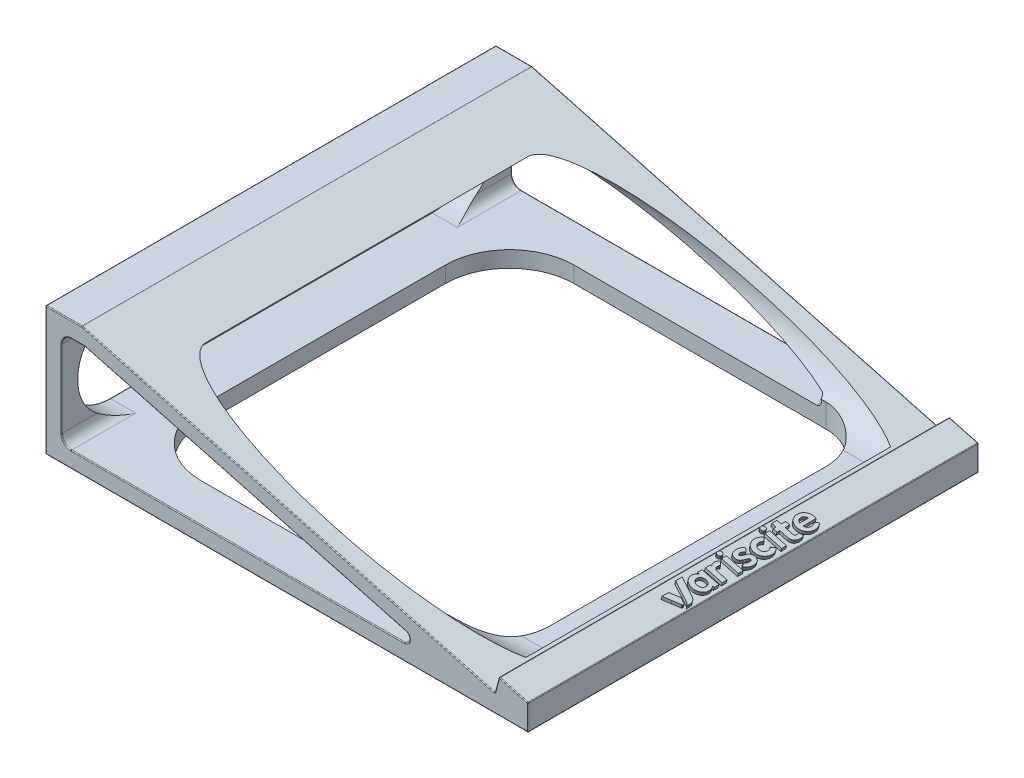
SolidWorks part; units mm, degrees
material "ABS"
ref_plane "Ebene vorne" through (0, 0, 0) normal (1, 0, 0) x (0, 1, 0)
ref_plane "Ebene oben" through (0, 0, 0) normal (0, 0, 1) x (0, 1, 0)
ref_plane "Ebene rechts" through (0, 0, 0) normal (0, 1, 0) x (-1, 0, 0)
sketch "Basis" plane through (0, 0, 0) normal (0, 0, 1) x (0, 1, 0)
  line L0 (0, 0) -> (0, 150)
  line L1 (0, 0) -> (8, 0)
  line L2 (8, 0) -> (10.4201, 9.032)
  line L3 (0, 150) -> (40, 150)
  line L4 (40, 150) -> (40, 138.7441)
  line L5 (40, 138.7441) -> (5.5905, 10.3261)
  line L6 (5.5905, 10.3261) -> (10.4201, 9.032)
  dimension "D1" = 15
  dimension "D2" = 90
  dimension "D3" = 8
  dimension "D4" = 150
  dimension "D5" = 15
  dimension "D6" = 40
  dimension "D8" = 5
extrude "Aufsatz-Linear austragen1" add sketch "Basis" along normal blind 140
sketch "Schnitt Boden" plane through (0.3591, 0, 0) normal (0, 1, 0) x (-1, 0, 0)
  line L0 (139.1032, 140) -> (139.1032, 0) construction
  line L4 (35.6851, 128) -> (114.1032, 128)
  line L6 (20.6851, 113) -> (20.6851, 27)
  line L7 (35.6851, 12) -> (114.1032, 12)
  line L8 (134.1032, 108) -> (134.1032, 32)
  line L9 (10.6851, 140) -> (139.1032, 140) construction
  line L10 (10.6851, 0) -> (139.1032, 0) construction
  line L11 (10.6851, 140) -> (10.6851, 0) construction
  arc A2 (35.6851, 128) -> (20.6851, 113) centre (35.6851, 113) ccw
  arc A3 (20.6851, 27) -> (35.6851, 12) centre (35.6851, 27) ccw
  arc A4 (134.1032, 32) -> (114.1032, 12) centre (114.1032, 32) cw
  arc A5 (134.1032, 108) -> (114.1032, 128) centre (114.1032, 108) ccw
  point P20 (10.6851, 70)
  dimension "D1" = 15
  dimension "D3" = 12
  dimension "D6" = 20
  dimension "D2" = 5
  dimension "D4" = 12
  dimension "D5" = 10
sketch "Schnitt Hinten" plane through (-150, 0, 0) normal (-1, 0, 0) x (0, -1, 0)
  line L0 (-20, 120) -> (-20, 20) construction
  line L1 (-5, 120) -> (-5, 20)
  line L2 (-35, 120) -> (-35, 20)
  line L3 (-40, 0) -> (0, 0) construction
  line L4 (0, 140) -> (0, 0) construction
  arc A0 (-5, 120) -> (-35, 120) centre (-20, 120) ccw
  arc A1 (-35, 20) -> (-5, 20) centre (-20, 20) ccw
  point P2 (-20, 70)
  dimension "D1" = 70
  dimension "D2" = 20
extrude "Schnitt Hinten austragen" cut sketch "Schnitt Hinten" against normal blind 136
extrude "Schnitt Boden austragen" cut sketch "Schnitt Boden" along normal blind 10
sketch "Schnitt Seite" plane through (0, 0, 140) normal (0, 0, 1) x (1, 0, 0)
  line L0 (-142, 35) -> (-137.7635, 35)
  line L1 (-137.7635, 35) -> (-37.9725, 8.2611)
  line L2 (-36.8607, 6.8122) -> (-36.8607, 6.5)
  line L3 (-38.3607, 5) -> (-142, 5)
  line L4 (-145, 8) -> (-145, 32)
  line L5 (-150, 40) -> (-150, 0) construction
  line L6 (-150, 0) -> (0, 0) construction
  line L7 (-10.3261, 5.5905) -> (-138.7441, 40) construction
  arc A0 (-145, 32) -> (-142, 35) centre (-142, 32) cw
  arc A1 (-142, 5) -> (-145, 8) centre (-142, 8) cw
  arc A2 (-38.3607, 5) -> (-36.8607, 6.5) centre (-38.3607, 6.5) ccw
  arc A3 (-36.8607, 6.8122) -> (-37.9725, 8.2611) centre (-38.3607, 6.8122) ccw
  dimension "D5" = 3
  dimension "D6" = 3
  dimension "D7" = 1.5
  dimension "D1" = 5
  dimension "D2" = 5
  dimension "D3" = 0
  dimension "D4" = 5
extrude "Schnitt Seite austragen" cut sketch "Schnitt Seite" against normal blind 140
fillet "Katenverrundung austragen" radius 0.25 43 edges at (-36.8607, 6.6561, 140) (0, 0, 70) (0, 4, 0) (-36.8607, 6.6561, 0) (-37.1707, 7.7253, 0) (-37.3001, 5.4393, 0) (-139.8817, 35, 0) (-87.868, 21.6305, 0) (-144.1213, 34.1213, 0) (-144.1213, 5.8787, 0) (-145, 20, 0) (-150, 35, 70) (-150, 20, 135) (-150, 20, 5) (-150, 5, 70) (-150, 0, 70) (-90.1804, 5, 0) (-75, 0, 0) (0, 8, 70) (-4.516, 9.2101, 0) (-9.679, 8.0053, 0) (-10.3261, 5.5905, 70) (-9.032, 10.4201, 70) (-138.7441, 40, 70) (-37.3001, 5.4393, 140) (-144.1213, 5.8787, 140) (-144.1213, 34.1213, 140) (-139.8817, 35, 140) (-87.868, 21.6305, 140) (-145, 20, 140) (-37.1707, 7.7253, 140) (-90.1804, 5, 140) (-75, 0, 140) (0, 4, 140) (-4.516, 9.2101, 140) (-9.679, 8.0053, 140) (-150, 20, 140) (-144.3721, 40, 140) (-74.5351, 22.7952, 140) (-74.5351, 22.7952, 0) (-144.3721, 40, 0) (-150, 20, 0) (-150, 40, 70)
sketch "Skizze Logo" plane through (2, 7.4641, 0) normal (0.2588, 0.9659, 0) x (-0.9659, 0.2588, 0)
  line L0 (8.7653, 83.336) -> (8.7223, 83.5503)
  line L1 (8.7223, 83.5503) -> (8.6617, 83.7574)
  line L2 (8.6617, 83.7574) -> (8.5841, 83.9565)
  line L3 (8.5841, 83.9565) -> (8.4904, 84.1471)
  line L4 (8.4904, 84.1471) -> (8.3812, 84.3284)
  line L5 (8.3812, 84.3284) -> (8.2572, 84.4998)
  line L6 (8.2572, 84.4998) -> (8.1193, 84.6607)
  line L7 (8.1193, 84.6607) -> (7.968, 84.8103)
  line L8 (7.968, 84.8103) -> (7.8042, 84.948)
  line L9 (7.8042, 84.948) -> (7.6286, 85.0731)
  line L10 (7.6286, 85.0731) -> (7.4418, 85.1851)
  line L11 (7.4418, 85.1851) -> (7.2447, 85.2831)
  line L12 (7.2447, 85.2831) -> (7.0379, 85.3666)
  line L13 (7.0379, 85.3666) -> (6.8221, 85.4349)
  line L14 (6.8221, 85.4349) -> (6.5982, 85.4873)
  line L15 (6.5982, 85.4873) -> (6.3668, 85.5232)
  line L16 (6.3668, 85.5232) -> (6.1055, 85.5395)
  line L17 (6.1055, 85.5395) -> (5.8095, 85.5358)
  line L18 (5.8095, 85.5358) -> (5.5207, 85.5139)
  line L19 (5.5207, 85.5139) -> (5.2806, 85.4757)
  line L20 (5.2806, 85.4757) -> (5.0781, 85.4227)
  line L21 (5.0781, 85.4227) -> (4.8833, 85.3574)
  line L22 (4.8833, 85.3574) -> (4.6967, 85.2803)
  line L23 (4.6967, 85.2803) -> (4.5186, 85.1917)
  line L24 (4.5186, 85.1917) -> (4.3495, 85.0921)
  line L25 (4.3495, 85.0921) -> (4.1898, 84.9818)
  line L26 (4.1898, 84.9818) -> (4.0398, 84.8613)
  line L27 (4.0398, 84.8613) -> (3.9, 84.731)
  line L28 (3.9, 84.731) -> (3.7708, 84.5913)
  line L29 (3.7708, 84.5913) -> (3.6526, 84.4425)
  line L30 (3.6526, 84.4425) -> (3.5458, 84.2852)
  line L31 (3.5458, 84.2852) -> (3.4507, 84.1196)
  line L32 (3.4507, 84.1196) -> (3.3679, 83.9462)
  line L33 (3.3679, 83.9462) -> (3.2976, 83.7654)
  line L34 (3.2976, 83.7654) -> (3.2404, 83.5777)
  line L35 (3.2404, 83.5777) -> (3.1965, 83.3833)
  line L36 (3.1965, 83.3833) -> (3.1685, 83.1466)
  line L37 (3.1685, 83.1466) -> (3.1596, 82.8688)
  line L38 (3.1596, 82.8688) -> (3.1699, 82.5946)
  line L39 (3.1699, 82.5946) -> (3.1992, 82.3684)
  line L40 (3.1992, 82.3684) -> (3.274, 82.0965)
  line L41 (3.274, 82.0965) -> (3.3828, 81.8376)
  line L42 (3.3828, 81.8376) -> (3.5252, 81.5928)
  line L43 (3.5252, 81.5928) -> (3.7004, 81.3632)
  line L44 (3.7004, 81.3632) -> (3.7878, 81.262)
  line L45 (3.7878, 81.262) -> (3.523, 81.262)
  line L46 (3.523, 81.262) -> (3.2582, 81.262)
  line L47 (3.2582, 81.262) -> (3.2582, 80.5244)
  line L48 (3.2582, 80.5244) -> (3.2582, 79.7869)
  line L49 (3.2582, 79.7869) -> (5.9706, 79.7869)
  line L50 (5.9706, 79.7869) -> (8.6831, 79.7869)
  line L51 (8.6831, 79.7869) -> (8.6831, 80.5244)
  line L52 (8.6831, 80.5244) -> (8.6831, 81.262)
  line L53 (8.6831, 81.262) -> (8.4181, 81.262)
  line L54 (8.4181, 81.262) -> (8.1531, 81.262)
  line L55 (8.1531, 81.262) -> (8.2585, 81.3751)
  line L56 (8.2585, 81.3751) -> (8.4117, 81.5635)
  line L57 (8.4117, 81.5635) -> (8.5405, 81.7728)
  line L58 (8.5405, 81.7728) -> (8.6441, 82.0005)
  line L59 (8.6441, 82.0005) -> (8.7221, 82.2444)
  line L60 (8.7221, 82.2444) -> (8.7738, 82.5022)
  line L61 (8.7738, 82.5022) -> (8.7986, 82.7716)
  line L62 (8.7986, 82.7716) -> (8.796, 83.0503)
  line L63 (8.796, 83.0503) -> (8.7653, 83.336)
  line L64 (7.4097, 82.2247) -> (7.3649, 82.0826)
  line L65 (7.3649, 82.0826) -> (7.3051, 81.9471)
  line L66 (7.3051, 81.9471) -> (7.2312, 81.8194)
  line L67 (7.2312, 81.8194) -> (7.1442, 81.7007)
  line L68 (7.1442, 81.7007) -> (7.0451, 81.5922)
  line L69 (7.0451, 81.5922) -> (6.9348, 81.495)
  line L70 (6.9348, 81.495) -> (6.8142, 81.4103)
  line L71 (6.8142, 81.4103) -> (6.6844, 81.3393)
  line L72 (6.6844, 81.3393) -> (6.5039, 81.2616)
  line L73 (6.5039, 81.2616) -> (6.342, 81.2133)
  line L74 (6.342, 81.2133) -> (6.1728, 81.1888)
  line L75 (6.1728, 81.1888) -> (5.9706, 81.1825)
  line L76 (5.9706, 81.1825) -> (5.8016, 81.1888)
  line L77 (5.8016, 81.1888) -> (5.6459, 81.2066)
  line L78 (5.6459, 81.2066) -> (5.5019, 81.2367)
  line L79 (5.5019, 81.2367) -> (5.3678, 81.2798)
  line L80 (5.3678, 81.2798) -> (5.2421, 81.3364)
  line L81 (5.2421, 81.3364) -> (5.123, 81.4072)
  line L82 (5.123, 81.4072) -> (5.0087, 81.493)
  line L83 (5.0087, 81.493) -> (4.8977, 81.5942)
  line L84 (4.8977, 81.5942) -> (4.8015, 81.6985)
  line L85 (4.8015, 81.6985) -> (4.7191, 81.8071)
  line L86 (4.7191, 81.8071) -> (4.65, 81.9208)
  line L87 (4.65, 81.9208) -> (4.594, 82.0402)
  line L88 (4.594, 82.0402) -> (4.5509, 82.1661)
  line L89 (4.5509, 82.1661) -> (4.5204, 82.2992)
  line L90 (4.5204, 82.2992) -> (4.5021, 82.4401)
  line L91 (4.5021, 82.4401) -> (4.4959, 82.5895)
  line L92 (4.4959, 82.5895) -> (4.5046, 82.7693)
  line L93 (4.5046, 82.7693) -> (4.5314, 82.9407)
  line L94 (4.5314, 82.9407) -> (4.5759, 83.103)
  line L95 (4.5759, 83.103) -> (4.6376, 83.2551)
  line L96 (4.6376, 83.2551) -> (4.716, 83.3962)
  line L97 (4.716, 83.3962) -> (4.8109, 83.5254)
  line L98 (4.8109, 83.5254) -> (4.9216, 83.6418)
  line L99 (4.9216, 83.6418) -> (5.0478, 83.7444)
  line L100 (5.0478, 83.7444) -> (5.1467, 83.8087)
  line L101 (5.1467, 83.8087) -> (5.2515, 83.8648)
  line L102 (5.2515, 83.8648) -> (5.4773, 83.9516)
  line L103 (5.4773, 83.9516) -> (5.7229, 84.0043)
  line L104 (5.7229, 84.0043) -> (5.9856, 84.022)
  line L105 (5.9856, 84.022) -> (6.2383, 84.0043)
  line L106 (6.2383, 84.0043) -> (6.474, 83.9522)
  line L107 (6.474, 83.9522) -> (6.6904, 83.8674)
  line L108 (6.6904, 83.8674) -> (6.885, 83.7516)
  line L109 (6.885, 83.7516) -> (7.0557, 83.6063)
  line L110 (7.0557, 83.6063) -> (7.2001, 83.4334)
  line L111 (7.2001, 83.4334) -> (7.3159, 83.2343)
  line L112 (7.3159, 83.2343) -> (7.4008, 83.0108)
  line L113 (7.4008, 83.0108) -> (7.4319, 82.8374)
  line L114 (7.4319, 82.8374) -> (7.4441, 82.6215)
  line L115 (7.4441, 82.6215) -> (7.4368, 82.4037)
  line L116 (7.4368, 82.4037) -> (7.4097, 82.2247)
  line L117 (8.7651, 50.6421) -> (8.7206, 50.846)
  line L118 (8.7206, 50.846) -> (8.6623, 51.0448)
  line L119 (8.6623, 51.0448) -> (8.5907, 51.238)
  line L120 (8.5907, 51.238) -> (8.5066, 51.4248)
  line L121 (8.5066, 51.4248) -> (8.4104, 51.6046)
  line L122 (8.4104, 51.6046) -> (8.3029, 51.7765)
  line L123 (8.3029, 51.7765) -> (8.1846, 51.94)
  line L124 (8.1846, 51.94) -> (8.0562, 52.0943)
  line L125 (8.0562, 52.0943) -> (7.9183, 52.2387)
  line L126 (7.9183, 52.2387) -> (7.7716, 52.3726)
  line L127 (7.7716, 52.3726) -> (7.6166, 52.4951)
  line L128 (7.6166, 52.4951) -> (7.4541, 52.6057)
  line L129 (7.4541, 52.6057) -> (7.2845, 52.7036)
  line L130 (7.2845, 52.7036) -> (7.1086, 52.7881)
  line L131 (7.1086, 52.7881) -> (6.9269, 52.8585)
  line L132 (6.9269, 52.8585) -> (6.7401, 52.9141)
  line L133 (6.7401, 52.9141) -> (6.4354, 52.975)
  line L134 (6.4354, 52.975) -> (6.1284, 53.0047)
  line L135 (6.1284, 53.0047) -> (5.8223, 53.0036)
  line L136 (5.8223, 53.0036) -> (5.5208, 52.9725)
  line L137 (5.5208, 52.9725) -> (5.2272, 52.9116)
  line L138 (5.2272, 52.9116) -> (4.9449, 52.8217)
  line L139 (4.9449, 52.8217) -> (4.6774, 52.7032)
  line L140 (4.6774, 52.7032) -> (4.428, 52.5566)
  line L141 (4.428, 52.5566) -> (4.1935, 52.3806)
  line L142 (4.1935, 52.3806) -> (3.9807, 52.1824)
  line L143 (3.9807, 52.1824) -> (3.7902, 51.9629)
  line L144 (3.7902, 51.9629) -> (3.6227, 51.7231)
  line L145 (3.6227, 51.7231) -> (3.4787, 51.464)
  line L146 (3.4787, 51.464) -> (3.359, 51.1866)
  line L147 (3.359, 51.1866) -> (3.264, 50.8919)
  line L148 (3.264, 50.8919) -> (3.1944, 50.5808)
  line L149 (3.1944, 50.5808) -> (3.1649, 50.3128)
  line L150 (3.1649, 50.3128) -> (3.1558, 49.9902)
  line L151 (3.1558, 49.9902) -> (3.1668, 49.6655)
  line L152 (3.1668, 49.6655) -> (3.1978, 49.3911)
  line L153 (3.1978, 49.3911) -> (3.244, 49.1706)
  line L154 (3.244, 49.1706) -> (3.3031, 48.959)
  line L155 (3.3031, 48.959) -> (3.3748, 48.7571)
  line L156 (3.3748, 48.7571) -> (3.4588, 48.5654)
  line L157 (3.4588, 48.5654) -> (3.5549, 48.3844)
  line L158 (3.5549, 48.3844) -> (3.6626, 48.2148)
  line L159 (3.6626, 48.2148) -> (3.7818, 48.0572)
  line L160 (3.7818, 48.0572) -> (3.9121, 47.9122)
  line L161 (3.9121, 47.9122) -> (4.0791, 47.7418)
  line L162 (4.0791, 47.7418) -> (4.504, 48.1792)
  line L163 (4.504, 48.1792) -> (4.9289, 48.6165)
  line L164 (4.9289, 48.6165) -> (4.7974, 48.7619)
  line L165 (4.7974, 48.7619) -> (4.7038, 48.8749)
  line L166 (4.7038, 48.8749) -> (4.6229, 48.9934)
  line L167 (4.6229, 48.9934) -> (4.5544, 49.1186)
  line L168 (4.5544, 49.1186) -> (4.4979, 49.2514)
  line L169 (4.4979, 49.2514) -> (4.4529, 49.3929)
  line L170 (4.4529, 49.3929) -> (4.419, 49.5442)
  line L171 (4.419, 49.5442) -> (4.3959, 49.7065)
  line L172 (4.3959, 49.7065) -> (4.3832, 49.8806)
  line L173 (4.3832, 49.8806) -> (4.3808, 50.054)
  line L174 (4.3808, 50.054) -> (4.389, 50.2147)
  line L175 (4.389, 50.2147) -> (4.4085, 50.3645)
  line L176 (4.4085, 50.3645) -> (4.4395, 50.505)
  line L177 (4.4395, 50.505) -> (4.4825, 50.6377)
  line L178 (4.4825, 50.6377) -> (4.5381, 50.7643)
  line L179 (4.5381, 50.7643) -> (4.6065, 50.8864)
  line L180 (4.6065, 50.8864) -> (4.6883, 51.0056)
  line L181 (4.6883, 51.0056) -> (4.8341, 51.1662)
  line L182 (4.8341, 51.1662) -> (5.0108, 51.3051)
  line L183 (5.0108, 51.3051) -> (5.2067, 51.4145)
  line L184 (5.2067, 51.4145) -> (5.4104, 51.4868)
  line L185 (5.4104, 51.4868) -> (5.4707, 51.5019)
  line L186 (5.4707, 51.5019) -> (5.4768, 49.4602)
  line L187 (5.4768, 49.4602) -> (5.4829, 47.4184)
  line L188 (5.4829, 47.4184) -> (5.5781, 47.3951)
  line L189 (5.5781, 47.3951) -> (5.7816, 47.3785)
  line L190 (5.7816, 47.3785) -> (6.1372, 47.3713)
  line L191 (6.1372, 47.3713) -> (6.5653, 47.3805)
  line L192 (6.5653, 47.3805) -> (6.6938, 47.3993)
  line L193 (6.6938, 47.3993) -> (6.8321, 47.4336)
  line L194 (6.8321, 47.4336) -> (7.0177, 47.4911)
  line L195 (7.0177, 47.4911) -> (7.1969, 47.561)
  line L196 (7.1969, 47.561) -> (7.3691, 47.6425)
  line L197 (7.3691, 47.6425) -> (7.534, 47.7353)
  line L198 (7.534, 47.7353) -> (7.691, 47.8389)
  line L199 (7.691, 47.8389) -> (7.8398, 47.9526)
  line L200 (7.8398, 47.9526) -> (7.9797, 48.0761)
  line L201 (7.9797, 48.0761) -> (8.1104, 48.2088)
  line L202 (8.1104, 48.2088) -> (8.2314, 48.3501)
  line L203 (8.2314, 48.3501) -> (8.3422, 48.4997)
  line L204 (8.3422, 48.4997) -> (8.4423, 48.6569)
  line L205 (8.4423, 48.6569) -> (8.5313, 48.8212)
  line L206 (8.5313, 48.8212) -> (8.6087, 48.9922)
  line L207 (8.6087, 48.9922) -> (8.6741, 49.1694)
  line L208 (8.6741, 49.1694) -> (8.7269, 49.3522)
  line L209 (8.7269, 49.3522) -> (8.7667, 49.5401)
  line L210 (8.7667, 49.5401) -> (8.7914, 49.7841)
  line L211 (8.7914, 49.7841) -> (8.7992, 50.0931)
  line L212 (8.7992, 50.0931) -> (8.7905, 50.4011)
  line L213 (8.7905, 50.4011) -> (8.7651, 50.6421)
  line L214 (7.5605, 49.7242) -> (7.5279, 49.6062)
  line L215 (7.5279, 49.6062) -> (7.4806, 49.4899)
  line L216 (7.4806, 49.4899) -> (7.4203, 49.3775)
  line L217 (7.4203, 49.3775) -> (7.3484, 49.2709)
  line L218 (7.3484, 49.2709) -> (7.2666, 49.1723)
  line L219 (7.2666, 49.1723) -> (7.1762, 49.0836)
  line L220 (7.1762, 49.0836) -> (7.0789, 49.007)
  line L221 (7.0789, 49.007) -> (6.9762, 48.9445)
  line L222 (6.9762, 48.9445) -> (6.842, 48.8814)
  line L223 (6.842, 48.8814) -> (6.7109, 48.8312)
  line L224 (6.7109, 48.8312) -> (6.6073, 48.802)
  line L225 (6.6073, 48.802) -> (6.5556, 48.8022)
  line L226 (6.5556, 48.8022) -> (6.5458, 49.2065)
  line L227 (6.5458, 49.2065) -> (6.5417, 50.1591)
  line L228 (6.5417, 50.1591) -> (6.5417, 51.502)
  line L229 (6.5417, 51.502) -> (6.6071, 51.4868)
  line L230 (6.6071, 51.4868) -> (6.8473, 51.3866)
  line L231 (6.8473, 51.3866) -> (6.9594, 51.3231)
  line L232 (6.9594, 51.3231) -> (7.0677, 51.2442)
  line L233 (7.0677, 51.2442) -> (7.1704, 51.1523)
  line L234 (7.1704, 51.1523) -> (7.2655, 51.0494)
  line L235 (7.2655, 51.0494) -> (7.3512, 50.9379)
  line L236 (7.3512, 50.9379) -> (7.4256, 50.82)
  line L237 (7.4256, 50.82) -> (7.4868, 50.6979)
  line L238 (7.4868, 50.6979) -> (7.5329, 50.5737)
  line L239 (7.5329, 50.5737) -> (7.5749, 50.3799)
  line L240 (7.5749, 50.3799) -> (7.5939, 50.1601)
  line L241 (7.5939, 50.1601) -> (7.5893, 49.9347)
  line L242 (7.5893, 49.9347) -> (7.5605, 49.7242)
  line L243 (8.7997, 69.5331) -> (8.7498, 69.7927)
  line L244 (8.7498, 69.7927) -> (8.6698, 70.0532)
  line L245 (8.6698, 70.0532) -> (8.5655, 70.2983)
  line L246 (8.5655, 70.2983) -> (8.4429, 70.5117)
  line L247 (8.4429, 70.5117) -> (8.3209, 70.6724)
  line L248 (8.3209, 70.6724) -> (8.1863, 70.8116)
  line L249 (8.1863, 70.8116) -> (8.0391, 70.9293)
  line L250 (8.0391, 70.9293) -> (7.8792, 71.0256)
  line L251 (7.8792, 71.0256) -> (7.7067, 71.1005)
  line L252 (7.7067, 71.1005) -> (7.5215, 71.154)
  line L253 (7.5215, 71.154) -> (7.3235, 71.186)
  line L254 (7.3235, 71.186) -> (7.1127, 71.1967)
  line L255 (7.1127, 71.1967) -> (6.8511, 71.1816)
  line L256 (6.8511, 71.1816) -> (6.6177, 71.1347)
  line L257 (6.6177, 71.1347) -> (6.5106, 71.0986)
  line L258 (6.5106, 71.0986) -> (6.4095, 71.0537)
  line L259 (6.4095, 71.0537) -> (6.314, 70.9996)
  line L260 (6.314, 70.9996) -> (6.2236, 70.9362)
  line L261 (6.2236, 70.9362) -> (6.138, 70.8631)
  line L262 (6.138, 70.8631) -> (6.0569, 70.78)
  line L263 (6.0569, 70.78) -> (5.9064, 70.5827)
  line L264 (5.9064, 70.5827) -> (5.7692, 70.3419)
  line L265 (5.7692, 70.3419) -> (5.6422, 70.0555)
  line L266 (5.6422, 70.0555) -> (5.5523, 69.7862)
  line L267 (5.5523, 69.7862) -> (5.4353, 69.3893)
  line L268 (5.4353, 69.3893) -> (5.2987, 68.9414)
  line L269 (5.2987, 68.9414) -> (5.2374, 68.78)
  line L270 (5.2374, 68.78) -> (5.1774, 68.6541)
  line L271 (5.1774, 68.6541) -> (5.1161, 68.5592)
  line L272 (5.1161, 68.5592) -> (5.0509, 68.4905)
  line L273 (5.0509, 68.4905) -> (4.9794, 68.4435)
  line L274 (4.9794, 68.4435) -> (4.8989, 68.4135)
  line L275 (4.8989, 68.4135) -> (4.822, 68.4009)
  line L276 (4.822, 68.4009) -> (4.7487, 68.4048)
  line L277 (4.7487, 68.4048) -> (4.6797, 68.4247)
  line L278 (4.6797, 68.4247) -> (4.616, 68.4599)
  line L279 (4.616, 68.4599) -> (4.5584, 68.5098)
  line L280 (4.5584, 68.5098) -> (4.508, 68.5737)
  line L281 (4.508, 68.5737) -> (4.4656, 68.651)
  line L282 (4.4656, 68.651) -> (4.432, 68.741)
  line L283 (4.432, 68.741) -> (4.4007, 68.9161)
  line L284 (4.4007, 68.9161) -> (4.3934, 69.187)
  line L285 (4.3934, 69.187) -> (4.4016, 69.3806)
  line L286 (4.4016, 69.3806) -> (4.4235, 69.5645)
  line L287 (4.4235, 69.5645) -> (4.4593, 69.7395)
  line L288 (4.4593, 69.7395) -> (4.5093, 69.9064)
  line L289 (4.5093, 69.9064) -> (4.5738, 70.0658)
  line L290 (4.5738, 70.0658) -> (4.653, 70.2185)
  line L291 (4.653, 70.2185) -> (4.7472, 70.3653)
  line L292 (4.7472, 70.3653) -> (4.8565, 70.5067)
  line L293 (4.8565, 70.5067) -> (5.0016, 70.679)
  line L294 (5.0016, 70.679) -> (4.5641, 71.1183)
  line L295 (4.5641, 71.1183) -> (4.1267, 71.5576)
  line L296 (4.1267, 71.5576) -> (3.9482, 71.3677)
  line L297 (3.9482, 71.3677) -> (3.8246, 71.2252)
  line L298 (3.8246, 71.2252) -> (3.7103, 71.0711)
  line L299 (3.7103, 71.0711) -> (3.6057, 70.9066)
  line L300 (3.6057, 70.9066) -> (3.511, 70.7327)
  line L301 (3.511, 70.7327) -> (3.4264, 70.5504)
  line L302 (3.4264, 70.5504) -> (3.3522, 70.361)
  line L303 (3.3522, 70.361) -> (3.2887, 70.1654)
  line L304 (3.2887, 70.1654) -> (3.236, 69.9648)
  line L305 (3.236, 69.9648) -> (3.1945, 69.7602)
  line L306 (3.1945, 69.7602) -> (3.1644, 69.5527)
  line L307 (3.1644, 69.5527) -> (3.1459, 69.3433)
  line L308 (3.1459, 69.3433) -> (3.1393, 69.1332)
  line L309 (3.1393, 69.1332) -> (3.1449, 68.9234)
  line L310 (3.1449, 68.9234) -> (3.1628, 68.715)
  line L311 (3.1628, 68.715) -> (3.1934, 68.509)
  line L312 (3.1934, 68.509) -> (3.2369, 68.3067)
  line L313 (3.2369, 68.3067) -> (3.3056, 68.0998)
  line L314 (3.3056, 68.0998) -> (3.404, 67.8696)
  line L315 (3.404, 67.8696) -> (3.4727, 67.7355)
  line L316 (3.4727, 67.7355) -> (3.5372, 67.6323)
  line L317 (3.5372, 67.6323) -> (3.6137, 67.5373)
  line L318 (3.6137, 67.5373) -> (3.7181, 67.4281)
  line L319 (3.7181, 67.4281) -> (3.8322, 67.3215)
  line L320 (3.8322, 67.3215) -> (3.9463, 67.2311)
  line L321 (3.9463, 67.2311) -> (4.063, 67.1559)
  line L322 (4.063, 67.1559) -> (4.1846, 67.0949)
  line L323 (4.1846, 67.0949) -> (4.3136, 67.0469)
  line L324 (4.3136, 67.0469) -> (4.4524, 67.0109)
  line L325 (4.4524, 67.0109) -> (4.6036, 66.9857)
  line L326 (4.6036, 66.9857) -> (4.7695, 66.9705)
  line L327 (4.7695, 66.9705) -> (5.0164, 66.9704)
  line L328 (5.0164, 66.9704) -> (5.2457, 67.0016)
  line L329 (5.2457, 67.0016) -> (5.4578, 67.0644)
  line L330 (5.4578, 67.0644) -> (5.6531, 67.1589)
  line L331 (5.6531, 67.1589) -> (5.8318, 67.2853)
  line L332 (5.8318, 67.2853) -> (5.9942, 67.4438)
  line L333 (5.9942, 67.4438) -> (6.1408, 67.6347)
  line L334 (6.1408, 67.6347) -> (6.2718, 67.858)
  line L335 (6.2718, 67.858) -> (6.3552, 68.0473)
  line L336 (6.3552, 68.0473) -> (6.4509, 68.3117)
  line L337 (6.4509, 68.3117) -> (6.5544, 68.6381)
  line L338 (6.5544, 68.6381) -> (6.6613, 69.0132)
  line L339 (6.6613, 69.0132) -> (6.7369, 69.255)
  line L340 (6.7369, 69.255) -> (6.8201, 69.4547)
  line L341 (6.8201, 69.4547) -> (6.9063, 69.6034)
  line L342 (6.9063, 69.6034) -> (6.9493, 69.6558)
  line L343 (6.9493, 69.6558) -> (6.9913, 69.692)
  line L344 (6.9913, 69.692) -> (7.0865, 69.7354)
  line L345 (7.0865, 69.7354) -> (7.1893, 69.7483)
  line L346 (7.1893, 69.7483) -> (7.2887, 69.731)
  line L347 (7.2887, 69.731) -> (7.3737, 69.6837)
  line L348 (7.3737, 69.6837) -> (7.4322, 69.6224)
  line L349 (7.4322, 69.6224) -> (7.4815, 69.5454)
  line L350 (7.4815, 69.5454) -> (7.5214, 69.4543)
  line L351 (7.5214, 69.4543) -> (7.5515, 69.3506)
  line L352 (7.5515, 69.3506) -> (7.5714, 69.2356)
  line L353 (7.5714, 69.2356) -> (7.5809, 69.1109)
  line L354 (7.5809, 69.1109) -> (7.5795, 68.978)
  line L355 (7.5795, 68.978) -> (7.5669, 68.8384)
  line L356 (7.5669, 68.8384) -> (7.5149, 68.5772)
  line L357 (7.5149, 68.5772) -> (7.476, 68.4556)
  line L358 (7.476, 68.4556) -> (7.4282, 68.3395)
  line L359 (7.4282, 68.3395) -> (7.3713, 68.2284)
  line L360 (7.3713, 68.2284) -> (7.3052, 68.1218)
  line L361 (7.3052, 68.1218) -> (7.144, 67.9204)
  line L362 (7.144, 67.9204) -> (7.0208, 67.7877)
  line L363 (7.0208, 67.7877) -> (7.451, 67.3403)
  line L364 (7.451, 67.3403) -> (7.8812, 66.8928)
  line L365 (7.8812, 66.8928) -> (7.9459, 66.9389)
  line L366 (7.9459, 66.9389) -> (8.0455, 67.0263)
  line L367 (8.0455, 67.0263) -> (8.1679, 67.1568)
  line L368 (8.1679, 67.1568) -> (8.291, 67.3055)
  line L369 (8.291, 67.3055) -> (8.3931, 67.4473)
  line L370 (8.3931, 67.4473) -> (8.5356, 67.7048)
  line L371 (8.5356, 67.7048) -> (8.654, 67.9958)
  line L372 (8.654, 67.9958) -> (8.744, 68.3076)
  line L373 (8.744, 68.3076) -> (8.8011, 68.6273)
  line L374 (8.8011, 68.6273) -> (8.817, 68.8351)
  line L375 (8.817, 68.8351) -> (8.822, 69.0826)
  line L376 (8.822, 69.0826) -> (8.8162, 69.3288)
  line L377 (8.8162, 69.3288) -> (8.7997, 69.5331)
  line L378 (9.3612, 56.8265) -> (8.6831, 56.8265)
  line L379 (8.6831, 56.8265) -> (8.6831, 57.2667)
  line L380 (8.6831, 57.2667) -> (8.6831, 57.7068)
  line L381 (8.6831, 57.7068) -> (8.0525, 57.7068)
  line L382 (8.0525, 57.7068) -> (7.422, 57.7068)
  line L383 (7.422, 57.7068) -> (7.422, 57.2667)
  line L384 (7.422, 57.2667) -> (7.422, 56.8265)
  line L385 (7.422, 56.8265) -> (6.2383, 56.8265)
  line L386 (6.2383, 56.8265) -> (5.3276, 56.8194)
  line L387 (5.3276, 56.8194) -> (4.8003, 56.8023)
  line L388 (4.8003, 56.8023) -> (4.5723, 56.7705)
  line L389 (4.5723, 56.7705) -> (4.3514, 56.7197)
  line L390 (4.3514, 56.7197) -> (4.1451, 56.6521)
  line L391 (4.1451, 56.6521) -> (3.961, 56.5698)
  line L392 (3.961, 56.5698) -> (3.7991, 56.4634)
  line L393 (3.7991, 56.4634) -> (3.6286, 56.3154)
  line L394 (3.6286, 56.3154) -> (3.4728, 56.1485)
  line L395 (3.4728, 56.1485) -> (3.3552, 55.9852)
  line L396 (3.3552, 55.9852) -> (3.2864, 55.8562)
  line L397 (3.2864, 55.8562) -> (3.2267, 55.7182)
  line L398 (3.2267, 55.7182) -> (3.1761, 55.5714)
  line L399 (3.1761, 55.5714) -> (3.1346, 55.4158)
  line L400 (3.1346, 55.4158) -> (3.1023, 55.2517)
  line L401 (3.1023, 55.2517) -> (3.0791, 55.079)
  line L402 (3.0791, 55.079) -> (3.0606, 54.7089)
  line L403 (3.0606, 54.7089) -> (3.0689, 54.4372)
  line L404 (3.0689, 54.4372) -> (3.0949, 54.1968)
  line L405 (3.0949, 54.1968) -> (3.1408, 53.9751)
  line L406 (3.1408, 53.9751) -> (3.2084, 53.7594)
  line L407 (3.2084, 53.7594) -> (3.3235, 53.5045)
  line L408 (3.3235, 53.5045) -> (3.3784, 53.4125)
  line L409 (3.3784, 53.4125) -> (3.4142, 53.3765)
  line L410 (3.4142, 53.3765) -> (3.9195, 53.5656)
  line L411 (3.9195, 53.5656) -> (4.4787, 53.7796)
  line L412 (4.4787, 53.7796) -> (4.5453, 53.8044)
  line L413 (4.5453, 53.8044) -> (4.4865, 53.9057)
  line L414 (4.4865, 53.9057) -> (4.4223, 54.0385)
  line L415 (4.4223, 54.0385) -> (4.3799, 54.1794)
  line L416 (4.3799, 54.1794) -> (4.3585, 54.3331)
  line L417 (4.3585, 54.3331) -> (4.357, 54.5041)
  line L418 (4.357, 54.5041) -> (4.3777, 54.7052)
  line L419 (4.3777, 54.7052) -> (4.4005, 54.7764)
  line L420 (4.4005, 54.7764) -> (4.437, 54.8517)
  line L421 (4.437, 54.8517) -> (4.5121, 54.9599)
  line L422 (4.5121, 54.9599) -> (4.6093, 55.0492)
  line L423 (4.6093, 55.0492) -> (4.7243, 55.1166)
  line L424 (4.7243, 55.1166) -> (4.8531, 55.1589)
  line L425 (4.8531, 55.1589) -> (5.258, 55.1781)
  line L426 (5.258, 55.1781) -> (6.1978, 55.1848)
  line L427 (6.1978, 55.1848) -> (7.422, 55.1848)
  line L428 (7.422, 55.1848) -> (7.422, 54.4829)
  line L429 (7.422, 54.4829) -> (7.422, 53.781)
  line L430 (7.422, 53.781) -> (8.0525, 53.781)
  line L431 (8.0525, 53.781) -> (8.6831, 53.781)
  line L432 (8.6831, 53.781) -> (8.6831, 54.4829)
  line L433 (8.6831, 54.4829) -> (8.6831, 55.1848)
  line L434 (8.6831, 55.1848) -> (9.3612, 55.1848)
  line L435 (9.3612, 55.1848) -> (10.0393, 55.1848)
  line L436 (10.0393, 55.1848) -> (10.0393, 56.0056)
  line L437 (10.0393, 56.0056) -> (10.0393, 56.8265)
  line L438 (10.0393, 56.8265) -> (9.3612, 56.8265)
  line L439 (8.8011, 63.6787) -> (8.771, 63.9006)
  line L440 (8.771, 63.9006) -> (8.7268, 64.1166)
  line L441 (8.7268, 64.1166) -> (8.6691, 64.3261)
  line L442 (8.6691, 64.3261) -> (8.5982, 64.5285)
  line L443 (8.5982, 64.5285) -> (8.5145, 64.7232)
  line L444 (8.5145, 64.7232) -> (8.4185, 64.9098)
  line L445 (8.4185, 64.9098) -> (8.3107, 65.0876)
  line L446 (8.3107, 65.0876) -> (8.1913, 65.2561)
  line L447 (8.1913, 65.2561) -> (8.061, 65.4148)
  line L448 (8.061, 65.4148) -> (7.92, 65.563)
  line L449 (7.92, 65.563) -> (7.7688, 65.7002)
  line L450 (7.7688, 65.7002) -> (7.6079, 65.8259)
  line L451 (7.6079, 65.8259) -> (7.4376, 65.9395)
  line L452 (7.4376, 65.9395) -> (7.2585, 66.0405)
  line L453 (7.2585, 66.0405) -> (7.0708, 66.1282)
  line L454 (7.0708, 66.1282) -> (6.8751, 66.2021)
  line L455 (6.8751, 66.2021) -> (6.6178, 66.2741)
  line L456 (6.6178, 66.2741) -> (6.3532, 66.3208)
  line L457 (6.3532, 66.3208) -> (6.0845, 66.3425)
  line L458 (6.0845, 66.3425) -> (5.8145, 66.3392)
  line L459 (5.8145, 66.3392) -> (5.5465, 66.3113)
  line L460 (5.5465, 66.3113) -> (5.2834, 66.2588)
  line L461 (5.2834, 66.2588) -> (5.0283, 66.1819)
  line L462 (5.0283, 66.1819) -> (4.7843, 66.0808)
  line L463 (4.7843, 66.0808) -> (4.5037, 65.9277)
  line L464 (4.5037, 65.9277) -> (4.2464, 65.7469)
  line L465 (4.2464, 65.7469) -> (4.0133, 65.5397)
  line L466 (4.0133, 65.5397) -> (3.8053, 65.3074)
  line L467 (3.8053, 65.3074) -> (3.6235, 65.051)
  line L468 (3.6235, 65.051) -> (3.4687, 64.7719)
  line L469 (3.4687, 64.7719) -> (3.342, 64.4711)
  line L470 (3.342, 64.4711) -> (3.2442, 64.1499)
  line L471 (3.2442, 64.1499) -> (3.1927, 63.8505)
  line L472 (3.1927, 63.8505) -> (3.1665, 63.4945)
  line L473 (3.1665, 63.4945) -> (3.1675, 63.1342)
  line L474 (3.1675, 63.1342) -> (3.1976, 62.8224)
  line L475 (3.1976, 62.8224) -> (3.2415, 62.6069)
  line L476 (3.2415, 62.6069) -> (3.2999, 62.3981)
  line L477 (3.2999, 62.3981) -> (3.3729, 62.196)
  line L478 (3.3729, 62.196) -> (3.4604, 62.0007)
  line L479 (3.4604, 62.0007) -> (3.5625, 61.8122)
  line L480 (3.5625, 61.8122) -> (3.679, 61.6305)
  line L481 (3.679, 61.6305) -> (3.8101, 61.4557)
  line L482 (3.8101, 61.4557) -> (3.9556, 61.2877)
  line L483 (3.9556, 61.2877) -> (4.066, 61.1687)
  line L484 (4.066, 61.1687) -> (4.5381, 61.6554)
  line L485 (4.5381, 61.6554) -> (5.0101, 62.1422)
  line L486 (5.0101, 62.1422) -> (4.9134, 62.2446)
  line L487 (4.9134, 62.2446) -> (4.8171, 62.3611)
  line L488 (4.8171, 62.3611) -> (4.7266, 62.4978)
  line L489 (4.7266, 62.4978) -> (4.6491, 62.6426)
  line L490 (4.6491, 62.6426) -> (4.5919, 62.7832)
  line L491 (4.5919, 62.7832) -> (4.5581, 62.9073)
  line L492 (4.5581, 62.9073) -> (4.5338, 63.0438)
  line L493 (4.5338, 63.0438) -> (4.514, 63.3367)
  line L494 (4.514, 63.3367) -> (4.5327, 63.6269)
  line L495 (4.5327, 63.6269) -> (4.5565, 63.76)
  line L496 (4.5565, 63.76) -> (4.5899, 63.8792)
  line L497 (4.5899, 63.8792) -> (4.6509, 64.0265)
  line L498 (4.6509, 64.0265) -> (4.7288, 64.1649)
  line L499 (4.7288, 64.1649) -> (4.8224, 64.2933)
  line L500 (4.8224, 64.2933) -> (4.9302, 64.4104)
  line L501 (4.9302, 64.4104) -> (5.0511, 64.5149)
  line L502 (5.0511, 64.5149) -> (5.1837, 64.6056)
  line L503 (5.1837, 64.6056) -> (5.3269, 64.6812)
  line L504 (5.3269, 64.6812) -> (5.4791, 64.7406)
  line L505 (5.4791, 64.7406) -> (5.5893, 64.7729)
  line L506 (5.5893, 64.7729) -> (5.69, 64.7923)
  line L507 (5.69, 64.7923) -> (5.9587, 64.8055)
  line L508 (5.9587, 64.8055) -> (6.1297, 64.8017)
  line L509 (6.1297, 64.8017) -> (6.283, 64.7871)
  line L510 (6.283, 64.7871) -> (6.4217, 64.7605)
  line L511 (6.4217, 64.7605) -> (6.5491, 64.7207)
  line L512 (6.5491, 64.7207) -> (6.6683, 64.6665)
  line L513 (6.6683, 64.6665) -> (6.7824, 64.5966)
  line L514 (6.7824, 64.5966) -> (6.8946, 64.51)
  line L515 (6.8946, 64.51) -> (7.0082, 64.4053)
  line L516 (7.0082, 64.4053) -> (7.1207, 64.2834)
  line L517 (7.1207, 64.2834) -> (7.2155, 64.1575)
  line L518 (7.2155, 64.1575) -> (7.293, 64.0265)
  line L519 (7.293, 64.0265) -> (7.3538, 63.8891)
  line L520 (7.3538, 63.8891) -> (7.3982, 63.744)
  line L521 (7.3982, 63.744) -> (7.4268, 63.5901)
  line L522 (7.4268, 63.5901) -> (7.4399, 63.426)
  line L523 (7.4399, 63.426) -> (7.4381, 63.2506)
  line L524 (7.4381, 63.2506) -> (7.4248, 63.1017)
  line L525 (7.4248, 63.1017) -> (7.4003, 62.957)
  line L526 (7.4003, 62.957) -> (7.3652, 62.8177)
  line L527 (7.3652, 62.8177) -> (7.32, 62.685)
  line L528 (7.32, 62.685) -> (7.265, 62.5602)
  line L529 (7.265, 62.5602) -> (7.2007, 62.4444)
  line L530 (7.2007, 62.4444) -> (7.1278, 62.3389)
  line L531 (7.1278, 62.3389) -> (7.0465, 62.2449)
  line L532 (7.0465, 62.2449) -> (6.9594, 62.1552)
  line L533 (6.9594, 62.1552) -> (7.4346, 61.6787)
  line L534 (7.4346, 61.6787) -> (7.9098, 61.2022)
  line L535 (7.9098, 61.2022) -> (8.0716, 61.371)
  line L536 (8.0716, 61.371) -> (8.2609, 61.5958)
  line L537 (8.2609, 61.5958) -> (8.4247, 61.847)
  line L538 (8.4247, 61.847) -> (8.5619, 62.1204)
  line L539 (8.5619, 62.1204) -> (8.671, 62.4121)
  line L540 (8.671, 62.4121) -> (8.7507, 62.7178)
  line L541 (8.7507, 62.7178) -> (8.7999, 63.0336)
  line L542 (8.7999, 63.0336) -> (8.8171, 63.3552)
  line L543 (8.8171, 63.3552) -> (8.8011, 63.6787)
  line L544 (9.2125, 87.2932) -> (5.409, 88.8313)
  line L545 (5.409, 88.8313) -> (3.9054, 89.4497)
  line L546 (3.9054, 89.4497) -> (3.2244, 89.7399)
  line L547 (3.2244, 89.7399) -> (3.0916, 89.8237)
  line L548 (3.0916, 89.8237) -> (2.9593, 89.9301)
  line L549 (2.9593, 89.9301) -> (2.8417, 90.0466)
  line L550 (2.8417, 90.0466) -> (2.753, 90.1607)
  line L551 (2.753, 90.1607) -> (2.6842, 90.2677)
  line L552 (2.6842, 90.2677) -> (2.693, 89.5777)
  line L553 (2.693, 89.5777) -> (2.7031, 89.1222)
  line L554 (2.7031, 89.1222) -> (2.7284, 88.8359)
  line L555 (2.7284, 88.8359) -> (2.7514, 88.7282)
  line L556 (2.7514, 88.7282) -> (2.7837, 88.629)
  line L557 (2.7837, 88.629) -> (2.8835, 88.4119)
  line L558 (2.8835, 88.4119) -> (2.9533, 88.2854)
  line L559 (2.9533, 88.2854) -> (3.0331, 88.1623)
  line L560 (3.0331, 88.1623) -> (3.2179, 87.9319)
  line L561 (3.2179, 87.9319) -> (3.4281, 87.7313)
  line L562 (3.4281, 87.7313) -> (3.5397, 87.6455)
  line L563 (3.5397, 87.6455) -> (3.654, 87.5712)
  line L564 (3.654, 87.5712) -> (4.6016, 87.1597)
  line L565 (4.6016, 87.1597) -> (6.5785, 86.3226)
  line L566 (6.5785, 86.3226) -> (8.5705, 85.4871)
  line L567 (8.5705, 85.4871) -> (9.5635, 85.0808)
  line L568 (9.5635, 85.0808) -> (9.579, 85.0784)
  line L569 (9.579, 85.0784) -> (9.5907, 85.09)
  line L570 (9.5907, 85.09) -> (9.6049, 85.2013)
  line L571 (9.6049, 85.2013) -> (9.611, 86.0999)
  line L572 (9.611, 86.0999) -> (9.611, 87.134)
  line L573 (9.611, 87.134) -> (9.2125, 87.2932)
  line L574 (8.7647, 76.2456) -> (8.7017, 76.4992)
  line L575 (8.7017, 76.4992) -> (8.6077, 76.7304)
  line L576 (8.6077, 76.7304) -> (8.4812, 76.9421)
  line L577 (8.4812, 76.9421) -> (8.3208, 77.1374)
  line L578 (8.3208, 77.1374) -> (8.2003, 77.2648)
  line L579 (8.2003, 77.2648) -> (8.4417, 77.2648)
  line L580 (8.4417, 77.2648) -> (8.6831, 77.2648)
  line L581 (8.6831, 77.2648) -> (8.6831, 78.0143)
  line L582 (8.6831, 78.0143) -> (8.6831, 78.7638)
  line L583 (8.6831, 78.7638) -> (5.9706, 78.7638)
  line L584 (5.9706, 78.7638) -> (3.2582, 78.7638)
  line L585 (3.2582, 78.7638) -> (3.2582, 78.0143)
  line L586 (3.2582, 78.0143) -> (3.2582, 77.2648)
  line L587 (3.2582, 77.2648) -> (4.8345, 77.2646)
  line L588 (4.8345, 77.2646) -> (6.0223, 77.2579)
  line L589 (6.0223, 77.2579) -> (6.5604, 77.2402)
  line L590 (6.5604, 77.2402) -> (6.7804, 77.188)
  line L591 (6.7804, 77.188) -> (6.9673, 77.107)
  line L592 (6.9673, 77.107) -> (7.0498, 77.0548)
  line L593 (7.0498, 77.0548) -> (7.1259, 76.9944)
  line L594 (7.1259, 76.9944) -> (7.2614, 76.8473)
  line L595 (7.2614, 76.8473) -> (7.3587, 76.7014)
  line L596 (7.3587, 76.7014) -> (7.4182, 76.5572)
  line L597 (7.4182, 76.5572) -> (7.4482, 76.3858)
  line L598 (7.4482, 76.3858) -> (7.4569, 76.1584)
  line L599 (7.4569, 76.1584) -> (7.4557, 75.9842)
  line L600 (7.4557, 75.9842) -> (7.4477, 75.8738)
  line L601 (7.4477, 75.8738) -> (7.4278, 75.7927)
  line L602 (7.4278, 75.7927) -> (7.3909, 75.7063)
  line L603 (7.3909, 75.7063) -> (7.3267, 75.5877)
  line L604 (7.3267, 75.5877) -> (7.2662, 75.5029)
  line L605 (7.2662, 75.5029) -> (7.2081, 75.4423)
  line L606 (7.2081, 75.4423) -> (7.7369, 74.9703)
  line L607 (7.7369, 74.9703) -> (8.2656, 74.4982)
  line L608 (8.2656, 74.4982) -> (8.3732, 74.6186)
  line L609 (8.3732, 74.6186) -> (8.4988, 74.7791)
  line L610 (8.4988, 74.7791) -> (8.6033, 74.9555)
  line L611 (8.6033, 74.9555) -> (8.6864, 75.1459)
  line L612 (8.6864, 75.1459) -> (8.7476, 75.3485)
  line L613 (8.7476, 75.3485) -> (8.7864, 75.5616)
  line L614 (8.7864, 75.5616) -> (8.8025, 75.7833)
  line L615 (8.8025, 75.7833) -> (8.7954, 76.0119)
  line L616 (8.7954, 76.0119) -> (8.7647, 76.2456)
  line L617 (5.9706, 60.2765) -> (3.2582, 60.2765)
  line L618 (3.2582, 60.2765) -> (3.2582, 59.527)
  line L619 (3.2582, 59.527) -> (3.2582, 58.7775)
  line L620 (3.2582, 58.7775) -> (5.9706, 58.7775)
  line L621 (5.9706, 58.7775) -> (8.6831, 58.7775)
  line L622 (8.6831, 58.7775) -> (8.6831, 59.527)
  line L623 (8.6831, 59.527) -> (8.6831, 60.2765)
  line L624 (8.6831, 60.2765) -> (5.9706, 60.2765)
  line L625 (5.9706, 73.7434) -> (3.2582, 73.7434)
  line L626 (3.2582, 73.7434) -> (3.2582, 72.9939)
  line L627 (3.2582, 72.9939) -> (3.2582, 72.2444)
  line L628 (3.2582, 72.2444) -> (5.9706, 72.2444)
  line L629 (5.9706, 72.2444) -> (8.6831, 72.2444)
  line L630 (8.6831, 72.2444) -> (8.6831, 72.9939)
  line L631 (8.6831, 72.9939) -> (8.6831, 73.7434)
  line L632 (8.6831, 73.7434) -> (5.9706, 73.7434)
  line L633 (7.9077, 92.992) -> (5.7038, 92.0112)
  line L634 (5.7038, 92.0112) -> (3.4773, 91.0029)
  line L635 (3.4773, 91.0029) -> (3.418, 90.9512)
  line L636 (3.418, 90.9512) -> (3.3737, 90.8863)
  line L637 (3.3737, 90.8863) -> (3.3449, 90.8121)
  line L638 (3.3449, 90.8121) -> (3.3316, 90.7327)
  line L639 (3.3316, 90.7327) -> (3.3343, 90.6521)
  line L640 (3.3343, 90.6521) -> (3.3531, 90.5741)
  line L641 (3.3531, 90.5741) -> (3.3883, 90.5029)
  line L642 (3.3883, 90.5029) -> (3.4402, 90.4425)
  line L643 (3.4402, 90.4425) -> (3.7195, 90.3049)
  line L644 (3.7195, 90.3049) -> (4.2878, 90.0465)
  line L645 (4.2878, 90.0465) -> (4.8561, 89.7968)
  line L646 (4.8561, 89.7968) -> (5.1352, 89.6848)
  line L647 (5.1352, 89.6848) -> (6.3496, 90.2178)
  line L648 (6.3496, 90.2178) -> (7.835, 90.8895)
  line L649 (7.835, 90.8895) -> (7.9217, 90.9309)
  line L650 (7.9217, 90.9309) -> (7.9217, 91.9615)
  line L651 (7.9217, 91.9615) -> (7.9176, 92.6893)
  line L652 (7.9176, 92.6893) -> (7.9077, 92.992)
  line L653 (10.7528, 73.1404) -> (10.7, 73.3007)
  line L654 (10.7, 73.3007) -> (10.6122, 73.4439)
  line L655 (10.6122, 73.4439) -> (10.492, 73.5667)
  line L656 (10.492, 73.5667) -> (10.3418, 73.6657)
  line L657 (10.3418, 73.6657) -> (10.2702, 73.6996)
  line L658 (10.2702, 73.6996) -> (10.2039, 73.7193)
  line L659 (10.2039, 73.7193) -> (10.0155, 73.7308)
  line L660 (10.0155, 73.7308) -> (9.8272, 73.7194)
  line L661 (9.8272, 73.7194) -> (9.761, 73.6997)
  line L662 (9.761, 73.6997) -> (9.6898, 73.6661)
  line L663 (9.6898, 73.6661) -> (9.5937, 73.6083)
  line L664 (9.5937, 73.6083) -> (9.5098, 73.5422)
  line L665 (9.5098, 73.5422) -> (9.4382, 73.4682)
  line L666 (9.4382, 73.4682) -> (9.3791, 73.3865)
  line L667 (9.3791, 73.3865) -> (9.3328, 73.2976)
  line L668 (9.3328, 73.2976) -> (9.2995, 73.2018)
  line L669 (9.2995, 73.2018) -> (9.2794, 73.0994)
  line L670 (9.2794, 73.0994) -> (9.2726, 72.9907)
  line L671 (9.2726, 72.9907) -> (9.2753, 72.8935)
  line L672 (9.2753, 72.8935) -> (9.2862, 72.8175)
  line L673 (9.2862, 72.8175) -> (9.309, 72.7456)
  line L674 (9.309, 72.7456) -> (9.3476, 72.6606)
  line L675 (9.3476, 72.6606) -> (9.4222, 72.5364)
  line L676 (9.4222, 72.5364) -> (9.5133, 72.434)
  line L677 (9.5133, 72.434) -> (9.6213, 72.3527)
  line L678 (9.6213, 72.3527) -> (9.7468, 72.2922)
  line L679 (9.7468, 72.2922) -> (9.8441, 72.2635)
  line L680 (9.8441, 72.2635) -> (9.9445, 72.2483)
  line L681 (9.9445, 72.2483) -> (10.0462, 72.2464)
  line L682 (10.0462, 72.2464) -> (10.1474, 72.2573)
  line L683 (10.1474, 72.2573) -> (10.2462, 72.2809)
  line L684 (10.2462, 72.2809) -> (10.3408, 72.3168)
  line L685 (10.3408, 72.3168) -> (10.4294, 72.3646)
  line L686 (10.4294, 72.3646) -> (10.5101, 72.4241)
  line L687 (10.5101, 72.4241) -> (10.575, 72.49)
  line L688 (10.575, 72.49) -> (10.632, 72.5684)
  line L689 (10.632, 72.5684) -> (10.6801, 72.6565)
  line L690 (10.6801, 72.6565) -> (10.7183, 72.7514)
  line L691 (10.7183, 72.7514) -> (10.7456, 72.8501)
  line L692 (10.7456, 72.8501) -> (10.7612, 72.9498)
  line L693 (10.7612, 72.9498) -> (10.7639, 73.0475)
  line L694 (10.7639, 73.0475) -> (10.7528, 73.1404)
  line L695 (10.7528, 59.6735) -> (10.6999, 59.834)
  line L696 (10.6999, 59.834) -> (10.612, 59.9773)
  line L697 (10.612, 59.9773) -> (10.4917, 60.0999)
  line L698 (10.4917, 60.0999) -> (10.3418, 60.1982)
  line L699 (10.3418, 60.1982) -> (10.2703, 60.2316)
  line L700 (10.2703, 60.2316) -> (10.2038, 60.2512)
  line L701 (10.2038, 60.2512) -> (10.0155, 60.2627)
  line L702 (10.0155, 60.2627) -> (9.8284, 60.2514)
  line L703 (9.8284, 60.2514) -> (9.7629, 60.2325)
  line L704 (9.7629, 60.2325) -> (9.6943, 60.2006)
  line L705 (9.6943, 60.2006) -> (9.5386, 60.0986)
  line L706 (9.5386, 60.0986) -> (9.4739, 60.0388)
  line L707 (9.4739, 60.0388) -> (9.418, 59.9732)
  line L708 (9.418, 59.9732) -> (9.3708, 59.9017)
  line L709 (9.3708, 59.9017) -> (9.3322, 59.8241)
  line L710 (9.3322, 59.8241) -> (9.2808, 59.6507)
  line L711 (9.2808, 59.6507) -> (9.2685, 59.5323)
  line L712 (9.2685, 59.5323) -> (9.2751, 59.4159)
  line L713 (9.2751, 59.4159) -> (9.2998, 59.3033)
  line L714 (9.2998, 59.3033) -> (9.3415, 59.1963)
  line L715 (9.3415, 59.1963) -> (9.3996, 59.0966)
  line L716 (9.3996, 59.0966) -> (9.4731, 59.0061)
  line L717 (9.4731, 59.0061) -> (9.5611, 58.9265)
  line L718 (9.5611, 58.9265) -> (9.6629, 58.8595)
  line L719 (9.6629, 58.8595) -> (9.7376, 58.8217)
  line L720 (9.7376, 58.8217) -> (9.8052, 58.8005)
  line L721 (9.8052, 58.8005) -> (9.8898, 58.7914)
  line L722 (9.8898, 58.7914) -> (10.0155, 58.7894)
  line L723 (10.0155, 58.7894) -> (10.1412, 58.7914)
  line L724 (10.1412, 58.7914) -> (10.2257, 58.8005)
  line L725 (10.2257, 58.8005) -> (10.2933, 58.8217)
  line L726 (10.2933, 58.8217) -> (10.3681, 58.8595)
  line L727 (10.3681, 58.8595) -> (10.479, 58.9336)
  line L728 (10.479, 58.9336) -> (10.5679, 59.0131)
  line L729 (10.5679, 59.0131) -> (10.6212, 59.0824)
  line L730 (10.6212, 59.0824) -> (10.667, 59.1592)
  line L731 (10.667, 59.1592) -> (10.7336, 59.3281)
  line L732 (10.7336, 59.3281) -> (10.7636, 59.5046)
  line L733 (10.7636, 59.5046) -> (10.7636, 59.591)
  line L734 (10.7636, 59.591) -> (10.7528, 59.6735)
extrude "Logo austragen" add sketch "Skizze Logo" along normal blind 1
